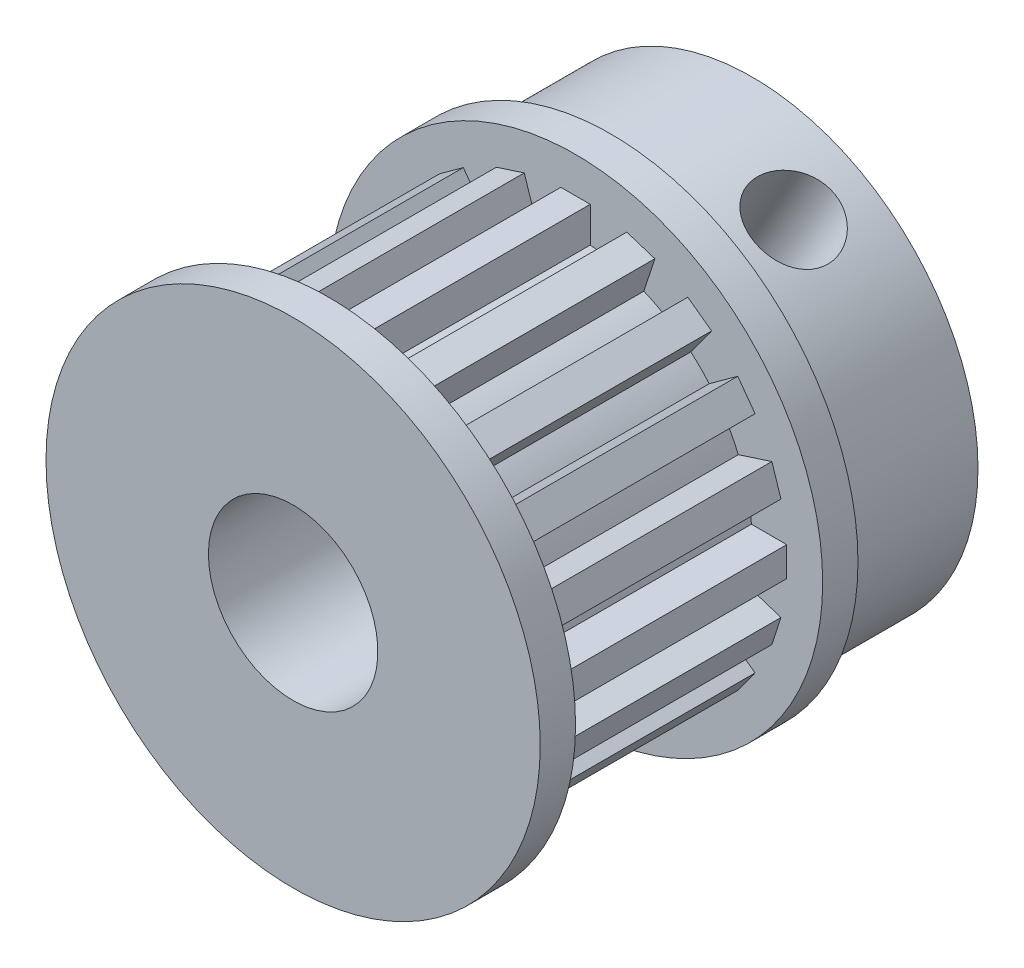
SolidWorks part; units mm, degrees
note: '?' marks a value the reader was unsure of.
material "ABS"
ref_plane "Plan de face" through (0, 0, 0) normal (0, 0, 1) x (1, 0, 0)
ref_plane "Plan de dessus" through (0, 0, 0) normal (0, 1, 0) x (1, 0, 0)
ref_plane "Plan de droite" through (0, 0, 0) normal (1, 0, 0) x (0, 0, -1)
sketch "Esquisse1" plane through (0, 0, 0) normal (0, 0, 1) x (1, 0, 0)
  line L0 (0.4167, 5.9826) -> (-0.4167, 5.9826)
  line L1 (2.245, 5.561) -> (1.936, 4.61)
  line L2 (2.245, 5.561) -> (1.4525, 5.8186)
  line L3 (1.4525, 5.8186) -> (1.1434, 4.8675)
  line L4 (3.8536, 4.5951) -> (3.2658, 3.7861)
  line L5 (0.4167, 5.9826) -> (0.4167, 4.9826)
  line L6 (3.8536, 4.5951) -> (3.1794, 5.0849)
  line L7 (-0.4167, 5.9826) -> (-0.4167, 4.9826)
  line L8 (3.1794, 5.0849) -> (2.5916, 4.2759)
  line L9 (5.085, 3.1794) -> (4.2759, 2.5916)
  line L10 (5.085, 3.1794) -> (4.5951, 3.8536)
  line L11 (4.5951, 3.8536) -> (3.7861, 3.2658)
  line L12 (5.8186, 1.4524) -> (4.8675, 1.1434)
  line L13 (5.8186, 1.4524) -> (5.561, 2.245)
  line L14 (5.561, 2.245) -> (4.61, 1.936)
  line L15 (5.9826, -0.4167) -> (4.9826, -0.4167)
  line L16 (5.9826, -0.4167) -> (5.9826, 0.4167)
  line L17 (5.9826, 0.4167) -> (4.9826, 0.4167)
  line L18 (5.561, -2.245) -> (4.61, -1.936)
  line L19 (5.561, -2.245) -> (5.8186, -1.4525)
  line L20 (5.8186, -1.4525) -> (4.8675, -1.1434)
  line L21 (4.5951, -3.8536) -> (3.7861, -3.2658)
  line L22 (4.5951, -3.8536) -> (5.0849, -3.1794)
  line L23 (5.0849, -3.1794) -> (4.2759, -2.5916)
  line L24 (3.1794, -5.085) -> (2.5916, -4.2759)
  line L25 (3.1794, -5.085) -> (3.8536, -4.5951)
  line L26 (3.8536, -4.5951) -> (3.2658, -3.7861)
  line L27 (1.4524, -5.8186) -> (1.1434, -4.8675)
  line L28 (1.4524, -5.8186) -> (2.245, -5.561)
  line L29 (2.245, -5.561) -> (1.936, -4.61)
  line L30 (-0.4167, -5.9826) -> (-0.4167, -4.9826)
  line L31 (-0.4167, -5.9826) -> (0.4167, -5.9826)
  line L32 (0.4167, -5.9826) -> (0.4167, -4.9826)
  line L33 (-2.245, -5.561) -> (-1.936, -4.61)
  line L34 (-2.245, -5.561) -> (-1.4525, -5.8186)
  line L35 (-1.4525, -5.8186) -> (-1.1434, -4.8675)
  line L36 (-3.8536, -4.5951) -> (-3.2658, -3.7861)
  line L37 (-3.8536, -4.5951) -> (-3.1794, -5.0849)
  line L38 (-3.1794, -5.0849) -> (-2.5916, -4.2759)
  line L39 (-5.085, -3.1794) -> (-4.2759, -2.5916)
  line L40 (-5.085, -3.1794) -> (-4.5951, -3.8536)
  line L41 (-4.5951, -3.8536) -> (-3.7861, -3.2658)
  line L42 (-5.8186, -1.4524) -> (-4.8675, -1.1434)
  line L43 (-5.8186, -1.4524) -> (-5.561, -2.245)
  line L44 (-5.561, -2.245) -> (-4.61, -1.936)
  line L45 (-5.9826, 0.4167) -> (-4.9826, 0.4167)
  line L46 (-5.9826, 0.4167) -> (-5.9826, -0.4167)
  line L47 (-5.9826, -0.4167) -> (-4.9826, -0.4167)
  line L48 (-5.561, 2.245) -> (-4.61, 1.936)
  line L49 (-5.561, 2.245) -> (-5.8186, 1.4525)
  line L50 (-5.8186, 1.4525) -> (-4.8675, 1.1434)
  line L51 (-4.5951, 3.8536) -> (-3.7861, 3.2658)
  line L52 (-4.5951, 3.8536) -> (-5.0849, 3.1794)
  line L53 (-5.0849, 3.1794) -> (-4.2759, 2.5916)
  line L54 (-3.1794, 5.085) -> (-2.5916, 4.2759)
  line L55 (-3.1794, 5.085) -> (-3.8536, 4.5951)
  line L56 (-3.8536, 4.5951) -> (-3.2658, 3.7861)
  line L57 (-1.4524, 5.8186) -> (-1.1434, 4.8675)
  line L58 (-1.4524, 5.8186) -> (-2.245, 5.561)
  line L59 (-2.245, 5.561) -> (-1.936, 4.61)
  circle A0 centre (0, 0) radius 2.4
  arc A1 (-0.4167, 4.9826) -> (-1.1434, 4.8675) centre (0, 0) ccw
  arc A2 (1.1434, 4.8675) -> (0.4167, 4.9826) centre (0, 0) ccw
  arc A3 (2.5916, 4.2759) -> (1.936, 4.61) centre (0, 0) ccw
  arc A4 (3.7861, 3.2658) -> (3.2658, 3.7861) centre (0, 0) ccw
  arc A5 (4.61, 1.936) -> (4.2759, 2.5916) centre (0, 0) ccw
  arc A6 (4.9826, 0.4167) -> (4.8675, 1.1434) centre (0, 0) ccw
  arc A7 (4.8675, -1.1434) -> (4.9826, -0.4167) centre (0, 0) ccw
  arc A8 (4.2759, -2.5916) -> (4.61, -1.936) centre (0, 0) ccw
  arc A9 (3.2658, -3.7861) -> (3.7861, -3.2658) centre (0, 0) ccw
  arc A10 (1.936, -4.61) -> (2.5916, -4.2759) centre (0, 0) ccw
  arc A11 (0.4167, -4.9826) -> (1.1434, -4.8675) centre (0, 0) ccw
  arc A12 (-1.1434, -4.8675) -> (-0.4167, -4.9826) centre (0, 0) ccw
  arc A13 (-2.5916, -4.2759) -> (-1.936, -4.61) centre (0, 0) ccw
  arc A14 (-3.7861, -3.2658) -> (-3.2658, -3.7861) centre (0, 0) ccw
  arc A15 (-4.61, -1.936) -> (-4.2759, -2.5916) centre (0, 0) ccw
  arc A16 (-4.9826, -0.4167) -> (-4.8675, -1.1434) centre (0, 0) ccw
  arc A17 (-4.8675, 1.1434) -> (-4.9826, 0.4167) centre (0, 0) ccw
  arc A18 (-4.2759, 2.5916) -> (-4.61, 1.936) centre (0, 0) ccw
  arc A19 (-3.2658, 3.7861) -> (-3.7861, 3.2658) centre (0, 0) ccw
  arc A20 (-1.936, 4.61) -> (-2.5916, 4.2759) centre (0, 0) ccw
  point P86 (0, 0)
  dimension "D1" = 4.8
  dimension "D2" = 10
  dimension "D3" = 20
  dimension "D4" = 1
extrude "Boss.-Extru.1" add sketch "Esquisse1" along normal blind 7
sketch "Esquisse2" plane through (0, 0, 7) normal (0, 0, 1) x (1, 0, 0)
  circle A0 centre (0, 0) radius 7
  dimension "D1" = 14
extrude "Boss.-Extru.2" add sketch "Esquisse2" along normal blind 1
sketch "Esquisse3" plane through (0, 0, 7) normal (0, 0, -1) x (-1, 0, 0)
  circle A0 centre (0, 0) radius 2.4
extrude "Enlèv. mat.-Extru.1" cut sketch "Esquisse3" against normal blind 1
sketch "Esquisse4" plane through (0, 0, 0) normal (0, 0, -1) x (-1, 0, 0)
  circle A0 centre (0, 0) radius 7
  dimension "D1" = 14
extrude "Boss.-Extru.3" add sketch "Esquisse4" along normal blind 1 contours A0
sketch "Esquisse5" plane through (0, 0, 0) normal (0, 0, 1) x (1, 0, 0)
  circle A0 centre (0, 0) radius 2.4
extrude "Enlèv. mat.-Extru.2" cut sketch "Esquisse5" against normal blind 1
sketch "Esquisse6" plane through (0, 0, -1) normal (0, 0, -1) x (-1, 0, 0)
  circle A0 centre (0, 0) radius 2.4
  circle A1 centre (0, 0) radius 6.4
  dimension "D1" = 4
extrude "Boss.-Extru.4" add sketch "Esquisse6" along normal blind 4
sketch "Esquisse7" plane through (0, 0, 0) normal (1, 0, 0) x (0, 0, -1)
  line L0 (5, 0) -> (1, 0) construction
  line L1 (5, -6.4) -> (5, 6.4) construction
  line L2 (1, -6.4) -> (1, 6.4) construction
  circle A0 centre (3, 0) radius 1.15
  dimension "D1" = 2.3
extrude "Enlèv. mat.-Extru.3" cut sketch "Esquisse7" against normal blind 8
sketch "Esquisse8" plane through (0, 0, 0) normal (0, 1, 0) x (1, 0, 0)
  line L0 (0, 0) -> (0, 11.975) construction
ref_axis "Axe1" through (0, 0, 0) along (0, 0, -1)?
pattern_circular "Répétition circulaire1" count 3 over 360 about axis through (0, 0, 0) along (0, 0, -1) of "Enlèv. mat.-Extru.3"
